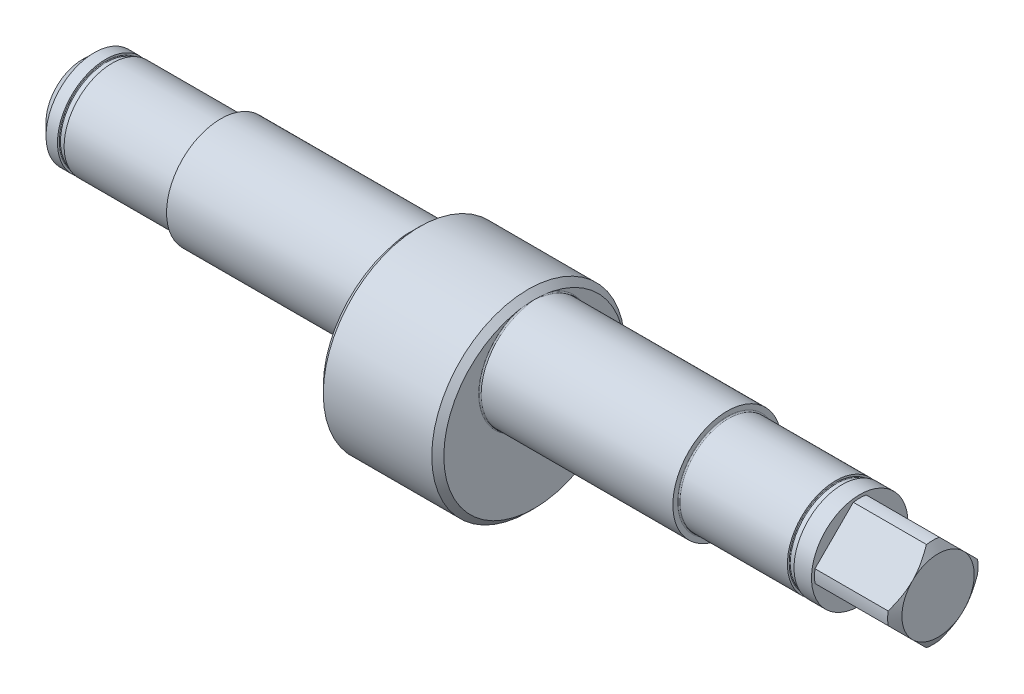
SolidWorks part; units mm, degrees
ref_plane "Piano frontale" through (0, 0, 0) normal (0, 0, 1) x (1, 0, 0)
ref_plane "Piano superiore" through (0, 0, 0) normal (0, 1, 0) x (1, 0, 0)
ref_plane "Piano destro" through (0, 0, 0) normal (1, 0, 0) x (0, 0, -1)
sketch "Schizzo1" plane through (0, 0, 0) normal (0, 0, 1) x (1, 0, 0)
  line L0 (0, 0) -> (0, 8)
  line L1 (0, 8) -> (23, 8)
  line L2 (23, 8) -> (23, 9)
  line L3 (23, 9) -> (107, 9)
  line L4 (107, 9) -> (107, 8)
  line L5 (107, 8) -> (142, 8)
  line L6 (142, 8) -> (142, 0)
  line L7 (142, 0) -> (0, 0)
  line L8 (0, 0) -> (-15.174, 0) construction
  dimension "D1" = 16
  dimension "D2" = 16
  dimension "D3" = 142
  dimension "D4" = 23
  dimension "D5" = 35
  dimension "D6" = 18
revolve "Rivoluzione1" add sketch "Schizzo1" angle 360 about L8
sketch "Schizzo2" plane through (0, 0, 0) normal (0, 0, 1) x (1, 0, 0)
  line L0 (17.6117, -6) -> (72.6815, -6) construction
  line L1 (23, 9) -> (23, -9) construction
  line L2 (55, -6) -> (75, -6)
  line L3 (55, -6) -> (55, -22)
  line L4 (55, -22) -> (75, -22)
  line L5 (75, -6) -> (75, -22)
  dimension "D1" = 6
  dimension "D2" = 32
  dimension "D3" = 32
  dimension "D4" = 20
revolve "Rivoluzione2" add sketch "Schizzo2" angle 360 about L0
sketch "Schizzo3" plane through (0, 0, 0) normal (0, 0, 1) x (1, 0, 0)
  line L0 (23, 9) -> (23, -9) construction
  line L1 (3.9, 8) -> (5, 8)
  line L2 (3.9, 8) -> (3.9, 7.6)
  line L3 (3.9, 7.6) -> (5, 7.6)
  line L4 (5, 8) -> (5, 7.6)
  line L5 (0, 0) -> (7.5787, 0) construction
  line L6 (0, 8) -> (0, -8) construction
  line L7 (23, 8) -> (0, 8) construction
  dimension "D1" = 18
  dimension "D2" = 1.1
  dimension "D3" = 15.2
revolve "Taglia-Rivoluzione1" cut sketch "Schizzo3" angle 360 about L5
sketch "Schizzo4" plane through (0, 0, 0) normal (0, 0, 1) x (1, 0, 0)
  line L0 (142, 8) -> (107, 8) construction
  line L1 (125, 8) -> (126.1, 8)
  line L2 (125, 8) -> (125, 7.6)
  line L3 (125, 7.6) -> (126.1, 7.6)
  line L4 (126.1, 8) -> (126.1, 7.6)
  line L5 (142, 0) -> (123.4637, 0) construction
  line L6 (142, -8) -> (142, 8) construction
  line L7 (107, -9) -> (107, 9) construction
  dimension "D1" = 18
  dimension "D2" = 1.1
  dimension "D3" = 15.2
revolve "Taglia-Rivoluzione2" cut sketch "Schizzo4" angle 360 about L5
fillet "Raccordo1" radius 0.1 4 edges at (126.1, 0, -7.6) (125, 0, -7.6) (3.9, 0, 7.6) (5, 0, 7.6)
sketch "Schizzo5" plane through (142, 0, 0) normal (1, 0, 0) x (0, 0, -1)
  line L0 (-8.4853, 0) -> (0, 8.4853)
  line L1 (-8.4853, 0) -> (0, -8.4853)
  line L2 (0, 8.4853) -> (8.4853, 0)
  line L3 (0, -8.4853) -> (8.4853, 0)
  line L4 (-8.4853, 0) -> (8.4853, 0) construction
  line L5 (0, 8.4853) -> (0, -8.4853) construction
  line L6 (0, 0) -> (18.0115, 0) construction
  circle A1 centre (0, 0) radius 7.5
  point P1 (0, 0)
  dimension "D3" = 15
  dimension "D1" = 135
  dimension "D2" = 12
extrude "Taglio-Estrusione1" cut sketch "Schizzo5" against normal blind 13 flip side to cut contours L2 A1 L0 L1 L3 region at (142, 0, 0)
sketch "Schizzo6" plane through (0, 0, 0) normal (0, 0, 1) x (1, 0, 0)
  line L0 (140.8453, 8) -> (142, 6)
  line L1 (142, 6) -> (142, 8)
  line L2 (142, 8) -> (140.8453, 8)
  line L3 (142, 1.0607) -> (142, 7.4246) construction
  line L4 (143.83, 0) -> (137.4077, 0) construction
  line L5 (125, 8) -> (107, 8) construction
  dimension "D1" = 6
  dimension "D2" = 30
revolve "Taglia-Rivoluzione3" cut sketch "Schizzo6" angle 360 about L4
chamfer "Smusso1" distance 2 angle 45 1 edges at (0, 0, -8)
chamfer "Smusso2" distance 1 angle 45 2 edges at (75, -6, 16) (55, -6, 16)
fillet "Raccordo2" radius 0.2 4 edges at (107, 0, -8) (75, 0, -9) (55, 0, 9) (23, 0, -8)
